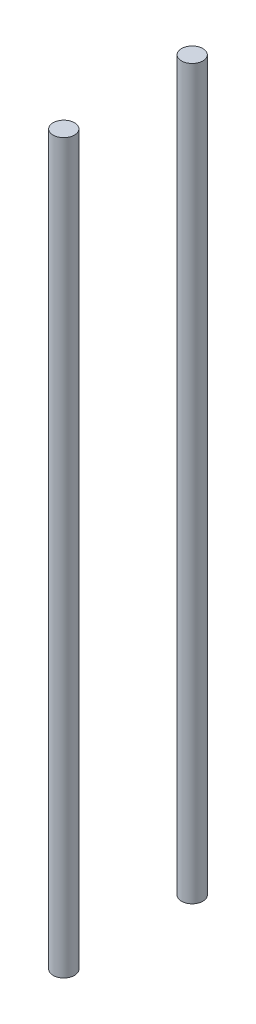
SolidWorks part; units mm, degrees
material "AISI 304"
ref_plane "Front Plane" through (0, 0, 0) normal (0, 0, 1) x (1, 0, 0)
ref_plane "Top Plane" through (0, 0, 0) normal (0, 1, 0) x (1, 0, 0)
ref_plane "Right Plane" through (0, 0, 0) normal (1, 0, 0) x (0, 0, -1)
ref_plane "Plane1" through (0, 2.5, 0) normal (0, -1, 0) x (0, 0, -1)
ref_plane "Plane2" through (0.2709, 2.5, -1.5473) normal (0.1719, 0, 0.9851) x (-0.9851, 0, 0.1719)
ref_axis "Axis1" through (0, 17.85, 0) along (0, -1, 0)
ref_plane "Plane5" through (0, 0, 0) normal (0, 1, 0) x (-1, 0, 0)
sketch "Sketch3" plane through (0, 0, 0) normal (0, 1, 0) x (-1, 0, 0)
  circle A0 centre (0, 1.5) radius 0.25
  circle A1 centre (0, -1.5) radius 0.25
extrude "Extrude1" add sketch "Sketch3" along normal blind 17
